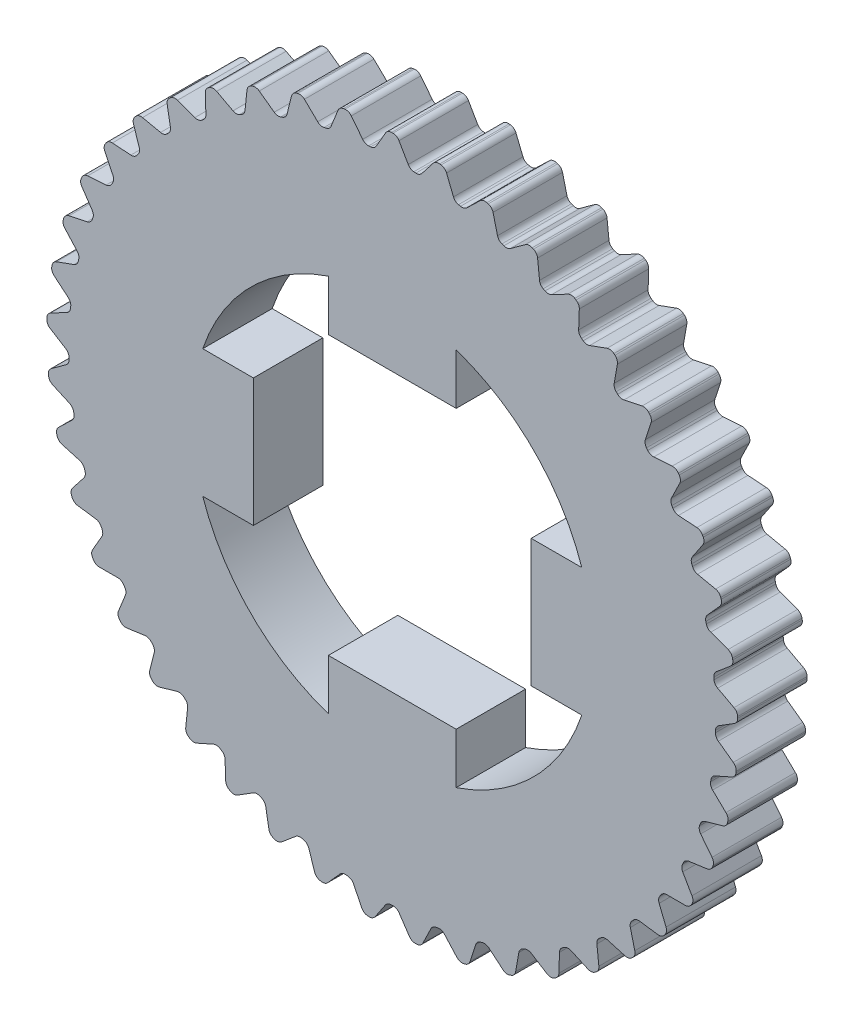
SolidWorks part; units mm, degrees
ref_plane "Front Plane" through (0, 0, 0) normal (0, 0, 1) x (1, 0, 0)
ref_plane "Top Plane" through (0, 0, 0) normal (0, 1, 0) x (1, 0, 0)
ref_plane "Right Plane" through (0, 0, 0) normal (1, 0, 0) x (0, 0, -1)
sketch "Sketch1" plane through (0, 0, 0) normal (0, 0, 1) x (1, 0, 0)
  line L0 (0, 0) -> (0, 15.8015) construction
  line L1 (0, 0) -> (-1.7718, 25.3385) construction
  line L2 (0.2159, 15.8015) -> (-0.2159, 15.8015)
  line L3 (-0.2159, 15.8015) -> (-0.8155, 14.763)
  line L4 (0.2159, 15.8015) -> (0.8155, 14.763)
  circle A0 centre (0, 0) radius 14.7855 construction
  arc A1 (-0.8155, 14.763) -> (-1.0314, 14.7494) centre (0, 0) ccw
  arc A2 (-1.0314, 14.7494) -> (1.0314, 14.7494) centre (0, 14.7855) ccw
  arc A3 (0.8155, 14.763) -> (1.0314, 14.7494) centre (0, 0) cw
  point P3 (0, 14.7855)
  dimension "D1" = 4
  dimension "D5" = 0.2159
  dimension "D2" = 1.016
  dimension "D3" = 0.2159
  dimension "D4" = 30
extrude "Boss-Extrude1" add sketch "Sketch1" along normal blind 3.175
sketch "Sketch6" plane through (0, 0, 0) normal (0, 0, 1) x (1, 0, 0)
  circle A0 centre (0, 0) radius 14.7855
  arc A1 (-0.8155, 14.763) -> (-1.0314, 14.7494) centre (0, 0) ccw construction
extrude "Boss-Extrude2" add sketch "Sketch6" along normal blind 3.175
fillet "Fillet1" radius 0.3175 4 edges at (-0.8155, 14.763, 1.5875) (0.8155, 14.763, 1.5875) (0.2159, 15.8015, 1.5875) (-0.2159, 15.8015, 1.5875)
pattern_circular "CirPattern3" count 45 over 360 about axis through (0, 0, 3.175) along (0, 0, 1) of "Boss-Extrude1", "Fillet1"
sketch "Sketch7" plane through (0, 0, 0) normal (0, 0, -1) x (-1, 0, 0)
  line L1 (-2.921, 12.446) -> (2.921, 12.446)
  line L2 (-2.921, 12.446) -> (-2.921, -12.446)
  line L3 (-2.921, -12.446) -> (2.921, -12.446)
  line L4 (2.921, 12.446) -> (2.921, -12.446)
  line L5 (-12.446, 2.921) -> (12.446, 2.921)
  line L6 (-12.446, 2.921) -> (-12.446, -2.921)
  line L7 (-12.446, -2.921) -> (12.446, -2.921)
  line L8 (12.446, 2.921) -> (12.446, -2.921)
  line L9 (-6.35, 2.921) -> (6.35, 2.921)
  line L10 (-6.35, 2.921) -> (-6.35, -2.921)
  line L11 (-6.35, -2.921) -> (6.35, -2.921)
  line L12 (6.35, 2.921) -> (6.35, -2.921)
  line L13 (-2.921, 6.35) -> (2.921, 6.35)
  line L14 (-2.921, 6.35) -> (-2.921, -6.35)
  line L15 (-2.921, -6.35) -> (2.921, -6.35)
  line L16 (2.921, 6.35) -> (2.921, -6.35)
  circle A0 centre (0, 0) radius 9.144
  point P7 (2.921, 0)
  point P8 (0, 12.446)
  point P13 (-12.446, 0)
  point P14 (0, 2.921)
  dimension "D1" = 18.288
  dimension "D2" = 24.892
  dimension "D3" = 5.842
  dimension "D4" = 5.842
  dimension "D5" = 24.892
  dimension "D6" = 12.7
  dimension "D7" = 6.35
  dimension "D8" = 12.7
  dimension "D9" = 6.35
extrude "Cut-Extrude1" cut sketch "Sketch7" against normal blind 3.175 contours L2 A0 L5 | L2 L7 L4 L5 | L5 A0 L4 | L4 A0 L7 | L7 A0 L2 | L13 L2 L5 L4 | L5 L10 L7 L2 | L2 L15 L4 L7 | L12 L5 L4 L7 region at (5.1303, 5.1303, 0) region at (-5.1303, 5.1303, 0) region at (0, 4.6355, 0) region at (0, 0, 0) region at (4.6355, 0, 0) region at (5.1303, -5.1303, 0) region at (-4.6355, 0, 0) region at (0, -4.6355, 0) region at (-5.1303, -5.1303, 0)
equation "\"D4@Sketch7\"=\"D3@Sketch7\""
equation "\"D5@Sketch7\"=\"D2@Sketch7\""
